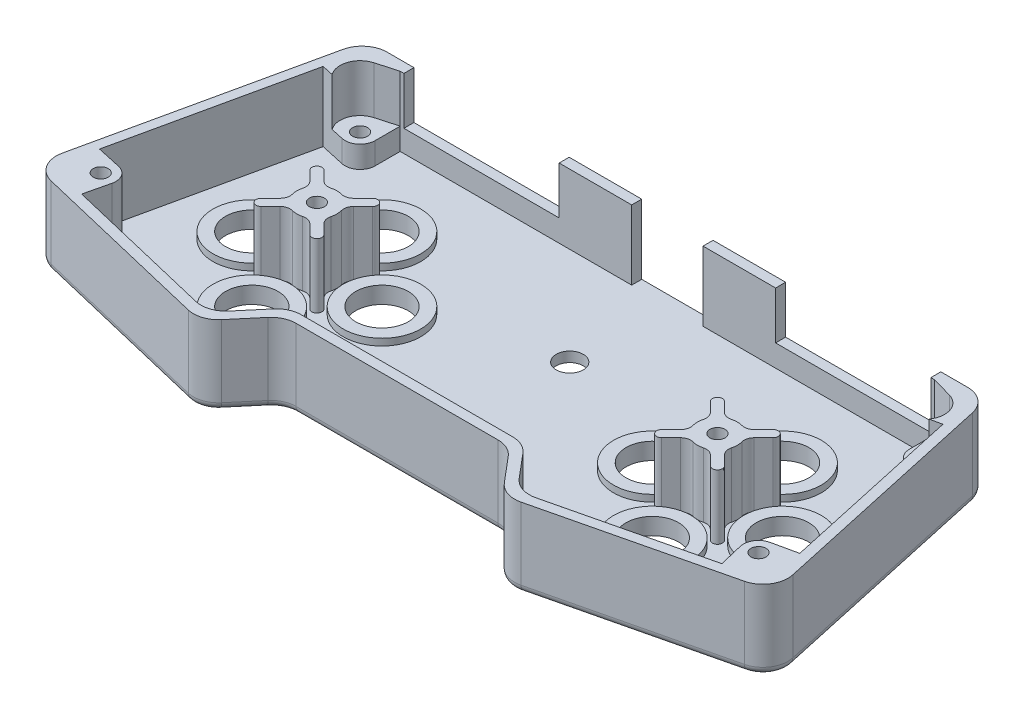
SolidWorks part; units mm, degrees
ref_plane "Front Plane" through (0, 0, 0) normal (0, 0, 1) x (1, 0, 0)
ref_plane "Top Plane" through (0, 0, 0) normal (0, 1, 0) x (1, 0, 0)
ref_plane "Right Plane" through (0, 0, 0) normal (1, 0, 0) x (0, 0, -1)
sketch "Sketch10" plane through (0, 0, 0) normal (0, 1, 0) x (1, 0, 0)
  line L0 (62, 32) -> (-62, 32)
  line L1 (-62, 32) -> (-74, -22.6992)
  line L2 (-74, -22.6992) -> (-30.236, -33.1736)
  line L3 (-30.236, -33.1736) -> (-22.5, -24)
  line L4 (-22.5, -24) -> (22.5, -24)
  line L5 (22.5, -24) -> (30.236, -33.1736)
  line L6 (30.236, -33.1736) -> (74, -22.6992)
  line L7 (74, -22.6992) -> (62, 32)
  line L8 (40, 13) -> (40, -13) construction
  line L9 (27, 0) -> (53, 0) construction
  line L10 (-40, 13) -> (-40, -13) construction
  line L11 (-53, 0) -> (-27, 0) construction
  line L12 (-27, 0) -> (27, 0) construction
  line L13 (0, 0) -> (0, 32) construction
  line L14 (0, 0) -> (0, -24) construction
  line L15 (74, -22.6992) -> (22.5, -24) construction
  line L16 (-22.5, -24) -> (-74, -22.6992) construction
  circle A0 centre (40, 13) radius 5.25
  circle A1 centre (27, 0) radius 5.25
  circle A2 centre (40, -13) radius 5.25
  circle A3 centre (53, 0) radius 5.25
  circle A4 centre (-40, 13) radius 5.25
  circle A5 centre (-53, 0) radius 5.25
  circle A6 centre (-40, -13) radius 5.25
  circle A7 centre (-27, 0) radius 5.25
  point P16 (40, 0)
  point P17 (-40, 0)
  dimension "D1" = 10.5
  dimension "D2" = 26
  dimension "D3" = 56
  dimension "D4" = 124
  dimension "D5" = 80
  dimension "D6" = 148
  dimension "D7" = 56
  dimension "D8" = 45
  dimension "D9" = 32
  dimension "D10" = 45
  dimension "D11" = 12
extrude "Boss-Extrude5" add sketch "Sketch10" along normal blind 2 separate body
sketch "Sketch11" plane through (0, 2, 0) normal (0, 1, 0) x (1, 0, 0)
  line L0 (-74, -22.6992) -> (-62, 32)
  line L1 (-62, 32) -> (62, 32)
  line L2 (62, 32) -> (74, -22.6992)
  line L3 (74, -22.6992) -> (30.236, -33.1736)
  line L4 (30.236, -33.1736) -> (22.5, -24)
  line L5 (22.5, -24) -> (-22.5, -24)
  line L6 (-22.5, -24) -> (-30.236, -33.1736)
  line L7 (-30.236, -33.1736) -> (-74, -22.6992)
  line L8 (-30.9699, -30.9414) -> (-71.6259, -21.2109)
  line L9 (-71.6259, -21.2109) -> (-60.3912, 30)
  line L10 (-60.3912, 30) -> (60.3912, 30)
  line L11 (60.3912, 30) -> (71.6259, -21.2109)
  line L12 (71.6259, -21.2109) -> (30.9699, -30.9414)
  line L13 (30.9699, -30.9414) -> (23.4296, -22)
  line L14 (23.4296, -22) -> (-23.4296, -22)
  line L15 (-23.4296, -22) -> (-30.9699, -30.9414)
  dimension "D1" = 2
extrude "Boss-Extrude7" add sketch "Sketch11" along direction (0, -1, 0) on the side of the normal offset from surface (13.875 mm away) 15.875 up to face at (-40, 0, 18.25)
fillet "Fillet4" radius 5 16 edges at (62, 7.9375, -32) (74, 7.9375, 22.6992) (30.236, 7.9375, 33.1736) (22.5, 7.9375, 24) (-22.5, 7.9375, 24) (-30.236, 7.9375, 33.1736) (-62, 7.9375, -32) (-74, 7.9375, 22.6992) (71.6259, 8.9375, 21.2109) (60.3912, 8.9375, -30) (30.9699, 8.9375, 30.9414) (23.4296, 8.9375, 22) (-23.4296, 8.9375, 22) (-30.9699, 8.9375, 30.9414) (-71.6259, 8.9375, 21.2109) (-60.3912, 8.9375, -30)
fillet "Fillet5" radius 1.5 16 edges at (30.509, 0, 32.3431) (26.1233, 0, 28.2966) (22.2835, 0, 24.4659) (0, 0, 24) (-22.2835, 0, 24.4659) (-26.1233, 0, 28.2966) (-30.509, 0, 32.3431) (-51.2316, 0, 28.1485) (-72.3012, 0, 21.6342) (-67.9053, 0, -5.0822) (-61.1119, 0, -30.896) (0, 0, -32) (61.1119, 0, -30.896) (67.9053, 0, -5.0822) (72.3012, 0, 21.6342) (51.2316, 0, 28.1485)
sketch "Sketch12" plane through (0, 2, 0) normal (0, 1, 0) x (1, 0, 0)
  line L0 (-61.8959, 23.1411) -> (-57.0121, 22.0697)
  line L1 (-61.2531, 26.0714) -> (-70.5746, -16.4188) construction
  line L2 (-53.3692, 25) -> (-53.3692, 30)
  line L3 (56.3692, 30) -> (-56.3692, 30) construction
  line L4 (-53.3692, 30) -> (-56.3692, 30)
  line L5 (-61.2531, 26.0714) -> (-61.8959, 23.1411)
  line L6 (-70.5746, -16.4188) -> (-69.9318, -13.4885)
  line L7 (-69.9318, -13.4885) -> (-65.0479, -14.5599)
  line L8 (-62.7732, -18.1885) -> (-63.937, -23.0512)
  line L9 (-66.8546, -22.3529) -> (-33.9684, -30.2238) construction
  line L10 (-63.937, -23.0512) -> (-66.8546, -22.3529)
  line L11 (0, 0) -> (0, 17.9434) construction
  line L12 (63.937, -23.0512) -> (66.8546, -22.3529)
  line L13 (62.7732, -18.1885) -> (63.937, -23.0512)
  line L14 (69.9318, -13.4885) -> (65.0479, -14.5599)
  line L15 (70.5746, -16.4188) -> (69.9318, -13.4885)
  line L16 (61.2531, 26.0714) -> (61.8959, 23.1411)
  line L17 (53.3692, 30) -> (56.3692, 30)
  line L18 (53.3692, 25) -> (53.3692, 30)
  line L19 (61.8959, 23.1411) -> (57.0121, 22.0697)
  arc A0 (-57.0121, 22.0697) -> (-53.3692, 25) centre (-56.3692, 25) ccw
  arc A1 (-56.3692, 30) -> (-61.2531, 26.0714) centre (-56.3692, 25) ccw
  arc A2 (-65.0479, -14.5599) -> (-62.7732, -18.1885) centre (-65.6908, -17.4902) cw
  arc A3 (-66.8546, -22.3529) -> (-70.5746, -16.4188) centre (-65.6908, -17.4902) cw
  circle A4 centre (-56.3692, 25) radius 1.5
  circle A5 centre (-65.6908, -17.4902) radius 1.5
  circle A6 centre (65.6908, -17.4902) radius 1.5
  circle A7 centre (56.3692, 25) radius 1.5
  arc A8 (66.8546, -22.3529) -> (70.5746, -16.4188) centre (65.6908, -17.4902) ccw
  arc A9 (65.0479, -14.5599) -> (62.7732, -18.1885) centre (65.6908, -17.4902) ccw
  arc A10 (56.3692, 30) -> (61.2531, 26.0714) centre (56.3692, 25) cw
  arc A11 (57.0121, 22.0697) -> (53.3692, 25) centre (56.3692, 25) cw
  dimension "D1" = 3
  dimension "D2" = 1.5
extrude "Boss-Extrude8" add sketch "Sketch12" along normal up to surface (13.875 mm away) up to face at (0, 15.875, 10.9337)
sketch "Sketch14" plane through (0, 0, -30) normal (0, 0, 1) x (1, 0, 0)
  line L0 (-53.3692, 15.875) -> (53.3692, 15.875) construction
  line L1 (-52.6192, 15.875) -> (-21.6192, 15.875)
  line L2 (-52.6192, 15.875) -> (-52.6192, 6.375)
  line L3 (-52.6192, 6.375) -> (-21.6192, 6.375)
  line L4 (-21.6192, 15.875) -> (-21.6192, 6.375)
  line L5 (0, 0) -> (0, 15.875) construction
  line L6 (21.6192, 15.875) -> (21.6192, 6.375)
  line L7 (52.6192, 6.375) -> (21.6192, 6.375)
  line L8 (52.6192, 15.875) -> (52.6192, 6.375)
  line L9 (52.6192, 15.875) -> (21.6192, 15.875)
  line L10 (-6.625, 15.03) -> (-6.625, 2.5) construction
  line L11 (-7.125, 15.875) -> (7.125, 15.875)
  line L12 (-7.125, 15.875) -> (-7.125, 2)
  line L13 (-7.125, 2) -> (7.125, 2)
  line L14 (7.125, 15.875) -> (7.125, 2)
  line L15 (53.3692, 2) -> (-53.3692, 2) construction
  dimension "D1" = 0.5
  dimension "D2" = 9.5
  dimension "D3" = 0.75
  dimension "D4" = 31
extrude "Cut-Extrude2" cut sketch "Sketch14" against normal through all
sketch "Sketch13" plane through (0, 15.875, 0) normal (0, 1, 0) x (1, 0, 0)
  line L0 (-57.4531, 28.8503) -> (-53.3692, 30)
  line L1 (-53.3692, 30) -> (-52.4618, 25.8555)
  line L2 (57.4531, 28.8503) -> (53.3692, 30)
  line L3 (53.3692, 30) -> (52.4618, 25.8555)
  arc A0 (-57.4531, 28.8503) -> (-52.4618, 25.8555) centre (-56.3692, 25) ccw
  arc A1 (52.4618, 25.8555) -> (57.4531, 28.8503) centre (56.3692, 25) ccw
  dimension "D1" = 8
extrude "Cut-Extrude1" cut sketch "Sketch13" against normal up to surface (9.5 mm away) up to face at (-37.1192, 6.375, -31)
sketch "Sketch15" plane through (0, 0, 0) normal (0, -1, 0) x (1, 0, 0)
  line L0 (0, -10.5) -> (0, -30.5) construction
  line L1 (-57.978, -30.5) -> (57.978, -30.5) construction
  circle A0 centre (0, -10.5) radius 2.7
  dimension "D2" = 5.4
  dimension "D1" = 20
extrude "Cut-Extrude3" cut sketch "Sketch15" against normal through all contours A0
sketch "Sketch16" plane through (0, 2, 0) normal (0, 1, 0) x (1, 0, 0)
  circle A0 centre (-40, 13) radius 7.75
  circle A1 centre (-40, 13) radius 5.25
  circle A2 centre (-27, 0) radius 7.75
  circle A3 centre (-27, 0) radius 5.25
  circle A4 centre (-53, 0) radius 5.25
  circle A5 centre (-53, 0) radius 7.75
  circle A6 centre (-40, -13) radius 5.25
  circle A7 centre (-40, -13) radius 7.75
  circle A8 centre (-40, 13) radius 5.25 construction
  circle A9 centre (-53, 0) radius 5.25 construction
  circle A10 centre (-40, -13) radius 5.25 construction
  circle A11 centre (-27, 0) radius 5.25 construction
  dimension "D1" = 2.5
extrude "Boss-Extrude9" add sketch "Sketch16" along normal blind 1.35
sketch "Sketch17" plane through (0, 2, 0) normal (0, 1, 0) x (1, 0, 0)
  line L0 (-43.4457, 2.0315) -> (-46.2741, 4.8599)
  line L3 (-44.8599, 6.2741) -> (-42.0315, 3.4457)
  line L4 (-37.9685, 3.4457) -> (-35.1401, 6.2741)
  line L5 (-33.7259, 4.8599) -> (-36.5543, 2.0315)
  line L6 (-36.5543, -2.0315) -> (-33.7259, -4.8599)
  line L7 (-35.1401, -6.2741) -> (-37.9685, -3.4457)
  line L8 (-42.0315, -3.4457) -> (-44.8599, -6.2741)
  line L9 (-46.2741, -4.8599) -> (-43.4457, -2.0315)
  line L10 (-45.567, -5.567) -> (-40, 0) construction
  line L11 (-40, 0) -> (-34.433, 5.567) construction
  line L12 (-34.433, -5.567) -> (-40, 0) construction
  line L13 (-45.567, 5.567) -> (-40, 0) construction
  line L14 (-45.567, 5.567) -> (-34.433, 5.567) construction
  line L15 (-40, 0) -> (0, 0) construction
  arc A0 (-43.4457, 2.0315) -> (-43.4457, -2.0315) centre (-40, 0) ccw
  arc A3 (-46.2741, 4.8599) -> (-44.8599, 6.2741) centre (-45.567, 5.567) cw
  arc A4 (-35.1401, 6.2741) -> (-33.7259, 4.8599) centre (-34.433, 5.567) cw
  arc A5 (-33.7259, -4.8599) -> (-35.1401, -6.2741) centre (-34.433, -5.567) cw
  arc A6 (-44.8599, -6.2741) -> (-46.2741, -4.8599) centre (-45.567, -5.567) cw
  arc A7 (-37.9685, 3.4457) -> (-42.0315, 3.4457) centre (-40, 0) ccw
  arc A8 (-36.5543, -2.0315) -> (-36.5543, 2.0315) centre (-40, 0) ccw
  arc A9 (-42.0315, -3.4457) -> (-37.9685, -3.4457) centre (-40, 0) ccw
  circle A10 centre (-40, 0) radius 1.5
  dimension "D1" = 40
  dimension "D4" = 8
  dimension "D5" = 3
  dimension "D2" = 2
  dimension "D3" = 4
extrude "Boss-Extrude10" add sketch "Sketch17" along normal offset from surface (12.875 mm away) 1 up to face at (-65.6908, 15.875, 15.9902)
fillet "Fillet6" radius 2 8 edges at (-43.4457, 8.4375, 2.0315) (-43.4457, 8.4375, -2.0315) (-42.0315, 8.4375, -3.4457) (-37.9685, 8.4375, -3.4457) (-36.5543, 8.4375, -2.0315) (-36.5543, 8.4375, 2.0315) (-37.9685, 8.4375, 3.4457) (-42.0315, 8.4375, 3.4457)
mirror "Mirror1" about plane through (0, 0, 0) normal (1, 0, 0) of "Fillet6", "Boss-Extrude9", "Boss-Extrude10"
